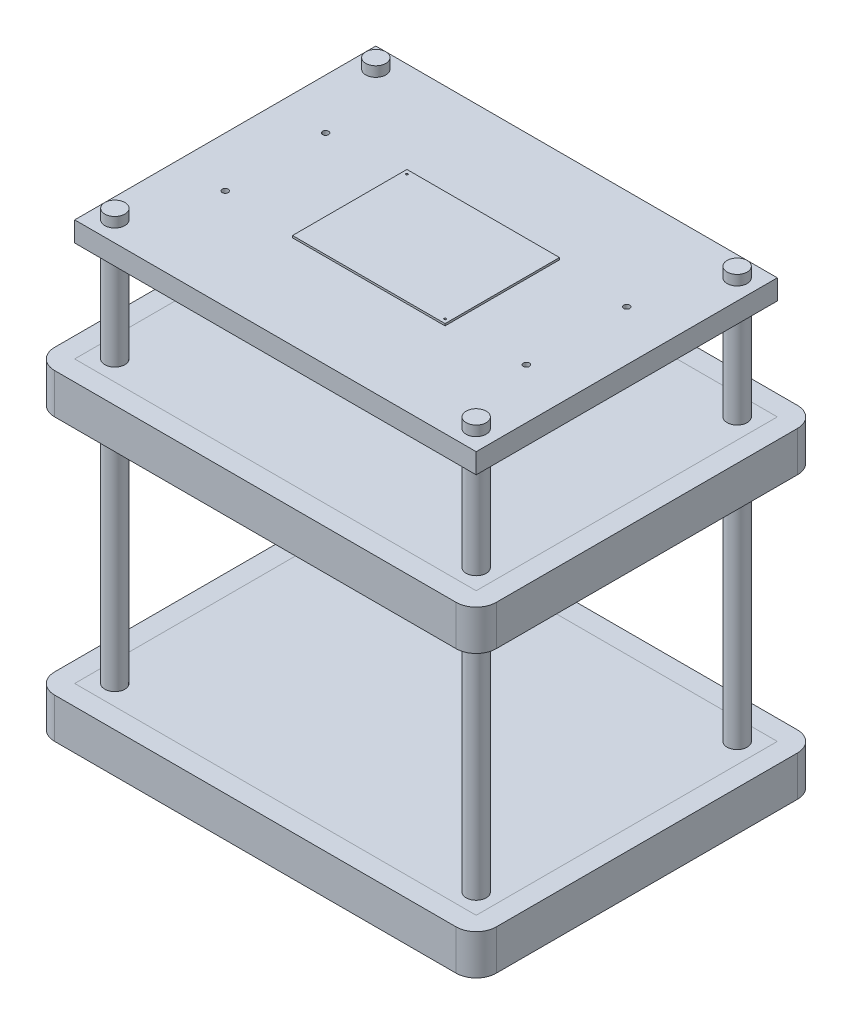
SolidWorks part; units mm, degrees
ref_plane "Front Plane" through (0, 0, 0) normal (0, 0, 1) x (1, 0, 0)
ref_plane "Top Plane" through (0, 0, 0) normal (0, 1, 0) x (1, 0, 0)
ref_plane "Right Plane" through (0, 0, 0) normal (1, 0, 0) x (0, 0, -1)
sketch "Sketch1" plane through (0, 0, 0) normal (0, 1, 0) x (1, 0, 0)
  line L1 (-100, 75) -> (100, 75)
  line L2 (-100, 75) -> (-100, -75)
  line L3 (-100, -75) -> (100, -75)
  line L4 (100, 75) -> (100, -75)
  line L5 (-100, 75) -> (100, -75) construction
  line L6 (-100, -75) -> (100, 75) construction
  point P0 (0, 0)
  dimension "D1" = 200
  dimension "D2" = 150
extrude "Boss-Extrude1" add sketch "Sketch1" along normal blind 10
sketch "Sketch2" plane through (0, 10, 0) normal (0, 1, 0) x (1, 0, 0)
  line L0 (-100, 75) -> (-100, -75) construction
  line L1 (100, 75) -> (-100, 75) construction
  line L2 (0, 73.0671) -> (0, 83.6614) construction
  line L3 (0, 83.6614) -> (0, -94.4748) construction
  line L4 (-110.8687, 0) -> (113.9791, 0) construction
  circle A0 centre (-90, 65) radius 5
  circle A1 centre (90, 65) radius 5
  circle A2 centre (90, -65) radius 5
  circle A3 centre (-90, -65) radius 5
  dimension "D1" = 10
  dimension "D2" = 10
  dimension "D3" = 10
extrude "Cut-Extrude1" cut sketch "Sketch2" against normal blind 10
ref_plane "Plane1" through (0, 140, 0) normal (0, 1, 0) x (1, 0, 0)
sketch "Sketch3" plane through (0, 140, 0) normal (0, 1, 0) x (1, 0, 0)
  line L1 (-100, 75) -> (100, 75)
  line L2 (-100, 75) -> (-100, -75)
  line L3 (-100, -75) -> (100, -75)
  line L4 (100, 75) -> (100, -75)
  line L5 (-100, 75) -> (100, -75) construction
  line L6 (-100, -75) -> (100, 75) construction
  circle A0 centre (-90, 65) radius 5
  circle A1 centre (90, 65) radius 5
  circle A2 centre (-90, -65) radius 5
  circle A3 centre (90, -65) radius 5
  point P0 (0, 0)
extrude "Boss-Extrude2" add sketch "Sketch3" along normal blind 10 separate body
ref_plane "Plane4" through (0, 200, 0) normal (0, 1, 0) x (1, 0, 0)
sketch "Sketch4" plane through (0, 200, 0) normal (0, 1, 0) x (1, 0, 0)
  line L1 (-100, 75) -> (100, 75)
  line L2 (-100, 75) -> (-100, -75)
  line L3 (-100, -75) -> (100, -75)
  line L4 (100, 75) -> (100, -75)
  line L5 (-100, 75) -> (100, -75) construction
  line L6 (-100, -75) -> (100, 75) construction
  circle A0 centre (-90, 65) radius 5
  circle A1 centre (90, 65) radius 5
  circle A2 centre (90, -65) radius 5
  circle A3 centre (-90, -65) radius 5
  point P1 (0, 0)
extrude "Boss-Extrude3" add sketch "Sketch4" along normal blind 10 separate body
sketch "Sketch5" plane through (0, 210, 0) normal (0, 1, 0) x (1, 0, 0)
  circle A0 centre (-90, -65) radius 5
sketch "Sketch17" plane through (0, 200, 0) normal (0, -1, 0) x (1, 0, 0)
  circle A0 centre (-90, -65) radius 5.3637
sketch "Sketch21" plane through (0, 10, 0) normal (0, 1, 0) x (1, 0, 0)
  circle A0 centre (-90, -65) radius 5
  circle A1 centre (-90, 65) radius 5
  circle A2 centre (90, 65) radius 5
  circle A3 centre (90, -65) radius 5
  dimension "D1" = 10
  dimension "D2" = 10
  dimension "D3" = 10
  dimension "D4" = 10
extrude "Boss-Extrude13" add sketch "Sketch21" along normal blind 205
sketch "Sketch22" plane through (0, 10, 0) normal (0, 1, 0) x (1, 0, 0)
  circle A0 centre (-90, 65) radius 5
  circle A1 centre (-90, -65) radius 5
  circle A2 centre (90, -65) radius 5
  circle A3 centre (90, 65) radius 5
  dimension "D1" = 10
  dimension "D2" = 10
  dimension "D3" = 10
  dimension "D4" = 10
extrude "Boss-Extrude14" add sketch "Sketch22" against normal blind 15
sketch "Sketch23" plane through (0, 210, 0) normal (0, 1, 0) x (1, 0, 0)
  line L0 (-100, 75) -> (-100, -75) construction
  line L1 (-140.155, 0) -> (119.4256, 0) construction
  line L2 (0, -82.5) -> (0, 82.5) construction
  circle A0 centre (-75, 25) radius 1.5
  circle A1 centre (-75, -25) radius 1.5
  circle A2 centre (75, -25) radius 1.5
  circle A3 centre (75, 25) radius 1.5
  dimension "D1" = 3
  dimension "D2" = 25
  dimension "D3" = 25
extrude "Cut-Extrude2" cut sketch "Sketch23" against normal blind 10
sketch "Sketch27" plane through (0, 210, 0) normal (0, 1, 0) x (1, 0, 0)
  line L0 (-38, 28.5) -> (38, -28.5) construction
  line L5 (-38, -28.5) -> (38, 28.5) construction
  line L7 (-38, 28.5) -> (38, 28.5)
  line L8 (-38, 28.5) -> (-38, -28.5)
  line L9 (-38, -28.5) -> (38, -28.5)
  line L10 (38, 28.5) -> (38, -28.5)
  circle A0 centre (-36, 26.5) radius 0.5
  circle A1 centre (36, -26.5) radius 0.5
  point P0 (-6.164, -10.787)
  point P5 (0, 0)
  point P11 (0, 0)
  dimension "D3" = 1
  dimension "D6" = 1
  dimension "D1" = 57
  dimension "D2" = 76
  dimension "D4" = 2
  dimension "D5" = 2
  dimension "D7" = 2
  dimension "D8" = 2
extrude "Boss-Extrude16" add sketch "Sketch27" along normal blind 1 contours L8 L7 L10 L9
sketch "Sketch30" plane through (0, 211, 0) normal (0, 1, 0) x (1, 0, 0)
  line L0 (-38, 28.5) -> (-38, -28.5) construction
  line L1 (-38, 28.5) -> (38, 28.5) construction
  line L2 (38, 28.5) -> (38, -28.5) construction
  line L3 (-38, -28.5) -> (38, -28.5) construction
  circle A0 centre (-36, 26.5) radius 0.5
  circle A1 centre (36, -26.5) radius 0.5
  dimension "D1" = 1
  dimension "D4" = 1
  dimension "D2" = 2
  dimension "D3" = 2
  dimension "D5" = 2
  dimension "D6" = 2
extrude "Cut-Extrude3" cut sketch "Sketch30" against normal blind 30
sketch "Sketch35" plane through (0, 0, 0) normal (0, -1, 0) x (-1, 0, 0)
  line L1 (100, -75) -> (-100, -75)
  line L2 (100, -75) -> (100, 75)
  line L3 (100, 75) -> (-100, 75)
  line L4 (-100, -75) -> (-100, 75)
  line L5 (100, -75) -> (-100, 75) construction
  line L6 (100, 75) -> (-100, -75) construction
  line L7 (110, -85) -> (-110, -85)
  line L8 (110, -85) -> (110, 85)
  line L9 (110, 85) -> (-110, 85)
  line L10 (-110, -85) -> (-110, 85)
  line L11 (110, -85) -> (-110, 85) construction
  line L12 (110, 85) -> (-110, -85) construction
  point P0 (0, 0)
  point P6 (0, 0)
  dimension "D1" = 150
  dimension "D2" = 170
  dimension "D3" = 200
  dimension "D4" = 220
extrude "Boss-Extrude19" add sketch "Sketch35" along normal mid plane 20 separate body
fillet "Fillet4" radius 10 4 edges at (110, 0, 85) (110, 0, -85) (-110, 0, 85) (-110, 0, -85)
sketch "Sketch39" plane through (0, 140, 0) normal (0, -1, 0) x (1, 0, 0)
  line L1 (-100, 75) -> (100, 75)
  line L2 (-100, 75) -> (-100, -75)
  line L3 (-100, -75) -> (100, -75)
  line L4 (100, 75) -> (100, -75)
  line L5 (-100, 75) -> (100, -75) construction
  line L6 (-100, -75) -> (100, 75) construction
  line L7 (-110, 85) -> (110, 85)
  line L8 (-110, 85) -> (-110, -85)
  line L9 (-110, -85) -> (110, -85)
  line L10 (110, 85) -> (110, -85)
  line L11 (-110, 85) -> (110, -85) construction
  line L12 (-110, -85) -> (110, 85) construction
  point P0 (0, 0)
  point P6 (0, 0)
  dimension "D1" = 150
  dimension "D2" = 200
  dimension "D3" = 170
  dimension "D4" = 220
extrude "Boss-Extrude20" add sketch "Sketch39" along normal mid plane 20 separate body
fillet "Fillet5" radius 10 4 edges at (110, 140, 85) (110, 140, -85) (-110, 140, -85) (-110, 140, 85)
sketch "Sketch42" plane through (0, 200, 0) normal (0, -1, 0) x (1, 0, 0)
  line L1 (-7.5, 10) -> (7.5, 10)
  line L2 (-7.5, 10) -> (-7.5, -10)
  line L3 (-7.5, -10) -> (7.5, -10)
  line L4 (7.5, 10) -> (7.5, -10)
  line L5 (-7.5, 10) -> (7.5, -10) construction
  line L6 (-7.5, -10) -> (7.5, 10) construction
  line L7 (-70.7403, -32.1967) -> (-15.7403, -32.1967)
  line L8 (-70.7403, -32.1967) -> (-70.7403, 32.8033)
  line L9 (-70.7403, 32.8033) -> (-15.7403, 32.8033)
  line L10 (-15.7403, -32.1967) -> (-15.7403, 32.8033)
  line L11 (-70.7403, -32.1967) -> (-15.7403, 32.8033) construction
  line L12 (-70.7403, 32.8033) -> (-15.7403, -32.1967) construction
  line L13 (15.7, 23.8618) -> (59, 23.8618)
  line L14 (15.7, 23.8618) -> (15.7, -19.4382)
  line L15 (15.7, -19.4382) -> (59, -19.4382)
  line L16 (59, 23.8618) -> (59, -19.4382)
  line L17 (15.7, 23.8618) -> (59, -19.4382) construction
  line L18 (15.7, -19.4382) -> (59, 23.8618) construction
  point P0 (0, 0)
  point P6 (-43.2403, 0.3033)
  point P11 (37.35, 2.2118)
  dimension "D1" = 20
  dimension "D2" = 15
  dimension "D3" = 65
  dimension "D4" = 55
  dimension "D5" = 43.3
  dimension "D6" = 43.3
  dimension "D7" = 8.2
extrude "Boss-Extrude23" add sketch "Sketch42" along normal blind 1
